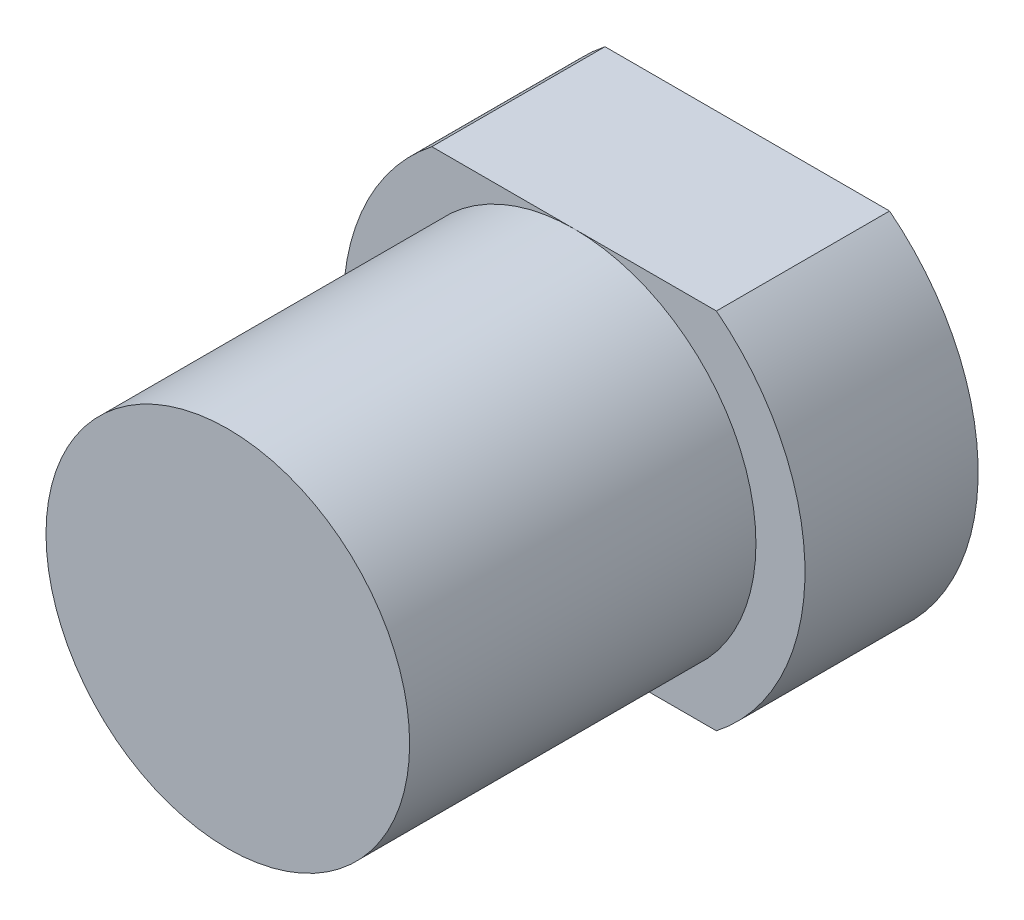
SolidWorks part; units mm, degrees
ref_plane "Front" through (0, 0, 0) normal (0, 0, 1) x (1, 0, 0)
ref_plane "Top" through (0, 0, 0) normal (0, 1, 0) x (1, 0, 0)
ref_plane "Right" through (0, 0, 0) normal (1, 0, 0) x (0, 0, -1)
sketch "Sketch1" plane through (0, 0, 0) normal (0, 0, 1) x (1, 0, 0)
  circle A0 centre (0, 0) radius 2
  dimension "D1" = 4
extrude "Boss-Extrude1" add sketch "Sketch1" along normal blind 1.5
sketch "Sketch2" plane through (0, 0, 1.5) normal (0, 0, 1) x (1, 0, 0)
  circle A0 centre (0, 0) radius 1.575
  dimension "D1" = 3.15
extrude "Boss-Extrude2" add sketch "Sketch2" along normal blind 3
sketch "Sketch3" plane through (0, 0, 1.5) normal (0, 0, 1) x (1, 0, 0)
  line L0 (-1.2326, -1.575) -> (1.2326, -1.575)
  line L1 (0, 0) -> (0, -2) construction
  circle A0 centre (0, 0) radius 2 construction
  circle A1 centre (0, 0) radius 1.575 construction
  arc A2 (-1.2326, -1.575) -> (1.2326, -1.575) centre (0, 0) ccw
  point P6 (0, -1.575)
extrude "Cut-Extrude1" cut sketch "Sketch3" against normal up to surface (1.5 mm away) up to face at (2, 0, 0)
mirror "Mirror1" about plane through (0, 0, 0) normal (0, 1, 0) of "Cut-Extrude1"
